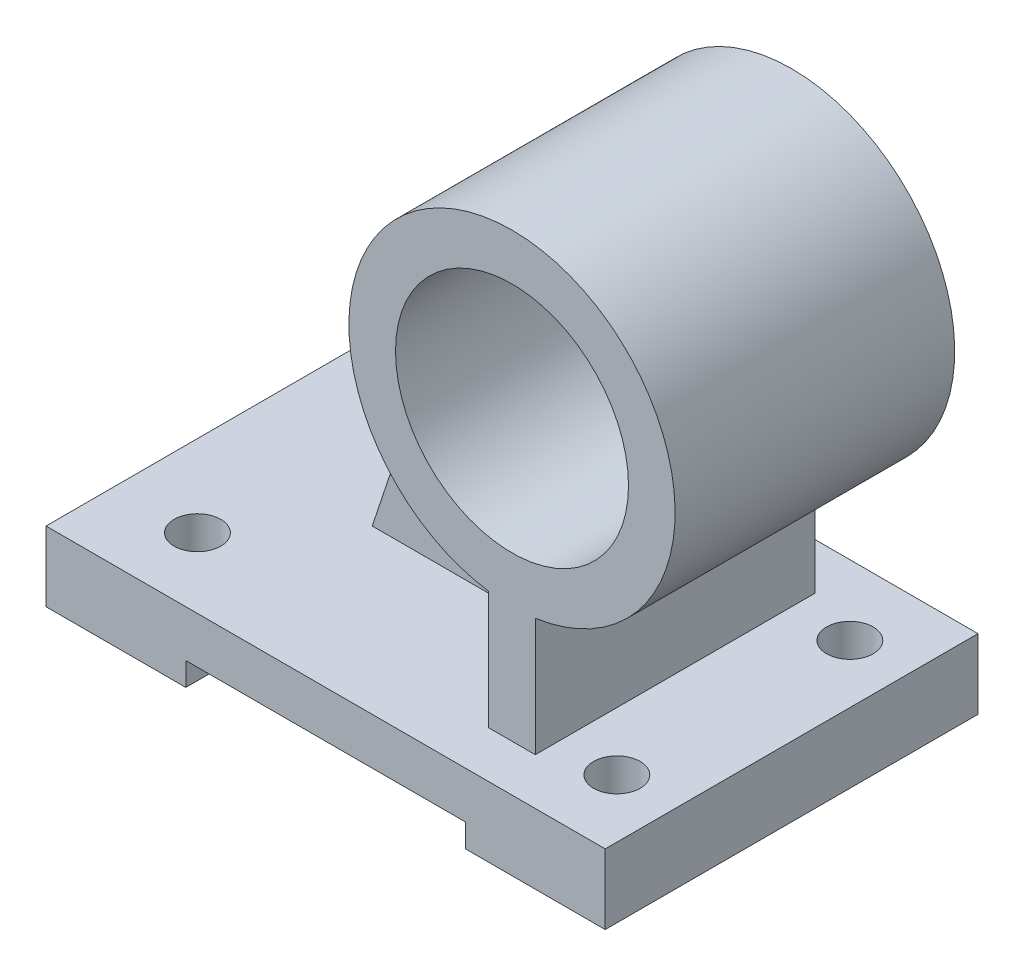
SolidWorks part; units mm, degrees
ref_plane "Front Plane" through (0, 0, 0) normal (0, 0, 1) x (1, 0, 0)
ref_plane "Top Plane" through (0, 0, 0) normal (0, 1, 0) x (1, 0, 0)
ref_plane "Right Plane" through (0, 0, 0) normal (1, 0, 0) x (0, 0, -1)
sketch "Sketch1" plane through (0, 0, 0) normal (0, 0, 1) x (1, 0, 0)
  line L1 (-5, -60) -> (5, -60)
  line L2 (-5, -60) -> (-5, -34.641)
  line L3 (5, -60) -> (5, -34.641)
  line L4 (0, -60) -> (30, -60)
  line L5 (30, -60) -> (30, -75)
  line L6 (30, -75) -> (0, -75)
  line L7 (-5, -60) -> (-90, -60)
  line L8 (-90, -60) -> (-90, -75)
  line L9 (-90, -75) -> (-60, -75)
  line L10 (-60, -75) -> (-60, -70)
  line L11 (-60, -70) -> (0, -70)
  line L12 (0, -70) -> (0, -75)
  line L13 (-35, 0) -> (-55, -60)
  circle A0 centre (0, 0) radius 25
  arc A1 (5, -34.641) -> (-5, -34.641) centre (0, 0) ccw
  point P4 (0, 0)
  point P8 (0, -60)
  point P20 (0, 0)
  point P21 (0, 0)
  point P22 (0, 0)
  dimension "D3" = 50
  dimension "D4" = 70
  dimension "D2" = 10
  dimension "D5" = 35
  dimension "D6" = 30
  dimension "D7" = 60
  dimension "D8" = 15
  dimension "D9" = 30
  dimension "D10" = 5
  dimension "D11" = 5
  dimension "D12" = 60
  dimension "D13" = 50
extrude "Boss-Extrude1" add sketch "Sketch1" along normal blind 30 and the other way blind 30 contours A1 L2 L1 L3 A0 region at (-3.82, -47.3205, 0)
extrude "Boss-Extrude2" add sketch "Sketch1<5>" along normal blind 5 and the other way blind 5 contours A1 L13 L7 L2 region at (-29.2401, -41.4007, 0)
sketch "Sketch1<5>" plane through (0, 0, 0) normal (0, 0, 1) x (1, 0, 0) same geometry as "Sketch1"
extrude "Boss-Extrude3" add sketch "Sketch1<6>" along normal blind 40 and the other way blind 40 contours L11 L12 L6 L5 L4 L1 L7 L8 L9 L10 region at (-30, -66.5, 0)
sketch "Sketch1<6>" plane through (0, 0, 0) normal (0, 0, 1) x (1, 0, 0) same geometry as "Sketch1"
sketch "Sketch2" plane through (0, -60, 0) normal (0, 1, 0) x (1, 0, 0)
  circle A0 centre (-72.5, 25) radius 5
  circle A1 centre (17.5, 25) radius 5
  circle A2 centre (17.5, -25) radius 5
  circle A3 centre (-72.5, -25) radius 5
  dimension "D1" = 2
  dimension "D3" = 10
  dimension "D4" = 50
  dimension "D5" = 90
  dimension "D2" = 2
extrude "Cut-Extrude1" cut sketch "Sketch2" against normal blind 40 contours A3 | A0 | A1 | A2
